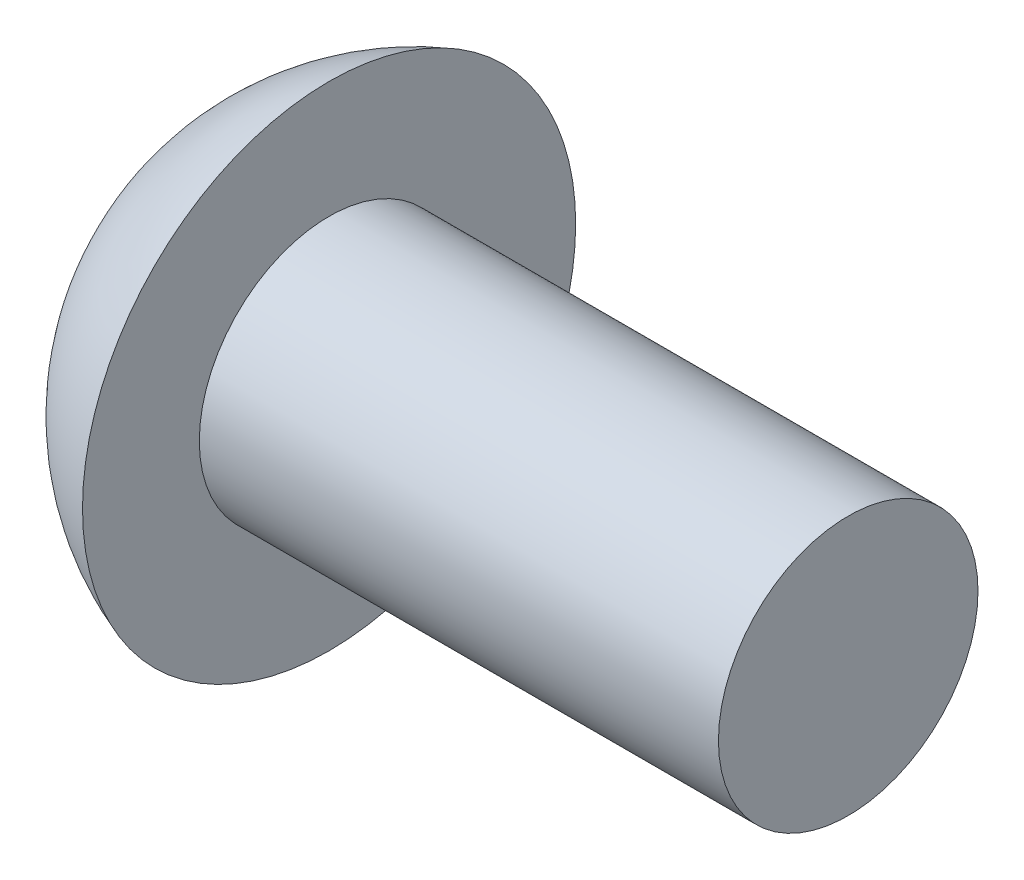
SolidWorks part; units mm, degrees
ref_plane "Front" through (0, 0, 0) normal (0, 0, 1) x (1, 0, 0)
ref_plane "Top" through (0, 0, 0) normal (0, 1, 0) x (1, 0, 0)
ref_plane "Right" through (0, 0, 0) normal (1, 0, 0) x (0, 0, -1)
sketch "Sketch1" plane through (0, 0, 0) normal (1, 0, 0) x (0, 0, -1)
  line L0 (0, 0) -> (1.4, 0) construction
  circle A0 centre (0, 0) radius 3.8
extrude "BaseHead" add sketch "Sketch1" along normal blind 2.2
sketch "Sketch2" plane through (2.2, 0, 0) normal (1, 0, 0) x (0, 0, -1)
  circle A0 centre (0, 0) radius 2
extrude "BaseBody" add sketch "Sketch2" along normal blind 8
cosmetic thread "ThreadCosmetic1" parameters "D1"=6.6, "THD_MINOR"=3.242
fillet "HeadFillet" [suppressed] radius 0.2
sketch "Sketch3" plane through (-13.4796, 2.4796, 0) normal (0, 0, 1) x (0, -1, 0)
  line L0 (2.4796, 13.4796) -> (2.4796, 41.0387) construction
  line L3 (-1.3204, 13.4796) -> (2.4796, 13.4796) construction
  line L5 (-6.3204, 15.6796) -> (-6.3204, 8.4796)
  line L6 (0.5446, 13.4796) -> (0.5446, 8.4796)
  line L7 (0.5446, 8.4796) -> (-6.3204, 8.4796)
  line L8 (-6.3204, 15.6796) -> (-1.3204, 15.6796)
  line L9 (-1.3204, 13.4796) -> (6.2796, 13.4796) construction
  arc A0 (-1.3204, 15.6796) -> (0.5446, 13.4796) centre (2.4796, 17.0104) ccw
  dimension "D2" = 5
  dimension "e" = 3.87
  dimension "D3" = 5
revolve "Cut-Revolve1" cut sketch "Sketch3" angle 360 about L0
sketch "Sketch4" plane through (0, 0, 0) normal (1, 0, 0) x (0, 0, -1)
  line L1 (1.4434, 0) -> (0.7217, 1.25)
  line L2 (0.7217, 1.25) -> (-0.7217, 1.25)
  line L3 (-0.7217, 1.25) -> (-1.4434, 0)
  line L4 (-1.4434, 0) -> (-0.7217, -1.25)
  line L5 (-0.7217, -1.25) -> (0.7217, -1.25)
  line L6 (0.7217, -1.25) -> (1.4434, 0)
  circle A0 centre (0, 0) radius 1.25 construction
  dimension "s" = 2.5
extrude "HexagonSocket" cut sketch "Sketch4" along normal blind 1.3
sketch "Sketch5" plane through (1.3, 0, 0) normal (-1, 0, 0) x (0, 0, 1)
  line L0 (0.7217, -1.25) -> (-0.7217, -1.25) construction
  line L1 (-0.7217, -1.25) -> (-1.4434, 0) construction
  line L2 (1.4434, 0) -> (0.7217, -1.25) construction
  line L3 (0.7217, 1.25) -> (1.4434, 0) construction
  line L4 (-1.4434, 0) -> (-0.7217, 1.25) construction
  line L5 (-0.7217, 1.25) -> (0.7217, 1.25) construction
  line L6 (0.7217, -1.25) -> (-0.7217, -1.25)
  line L7 (-0.7217, -1.25) -> (-1.4434, 0)
  line L8 (1.4434, 0) -> (0.7217, -1.25)
  line L9 (0.7217, 1.25) -> (1.4434, 0)
  line L10 (-1.4434, 0) -> (-0.7217, 1.25)
  line L11 (-0.7217, 1.25) -> (0.7217, 1.25)
extrude "Cut-Extrude2" cut sketch "Sketch5" against normal blind 5 draft 60
sketch "Sketch6" plane through (0, 0, 0) normal (0, 0, 1) x (1, 0, 0)
  line L0 (10.2, 1.6718) -> (10.3895, 2)
  line L1 (10.3895, 2) -> (10.3895, 2.379)
  line L2 (10.3895, 2.379) -> (10.0105, 2.379)
  line L3 (10.0105, 2.379) -> (10.0105, 2)
  line L4 (10.0105, 2) -> (10.2, 1.6718)
  line L5 (0, 0) -> (24.7294, 0) construction
  line L6 (10.2, -2) -> (10.2, 2) construction
  dimension "D1" = 0.379
  dimension "D2" = 4
revolve "Cut-Revolve10" [suppressed] cut sketch "Sketch6" angle 360 about L5
pattern_linear "LPattern10" [suppressed] count 16 spacing 0.4548 along (-1, 0, 0) of bodies 106
equation "\"D1@ThreadCosmetic1\" = \"l@BaseBody\" - \"a@Sketch1\""
equation "\"D2@Sketch6\" = \"d@Sketch2\""
equation "\"D1@Sketch6\" =  (\"d@Sketch2\" - \"THD_MINOR@ThreadCosmetic1\" )  / 2"
equation "\"D3@LPattern10\" = \"D1@Sketch6\" * 1.2"
equation "\"D1@LPattern10\" = \"D1@ThreadCosmetic1\" / \"D3@LPattern10\" + 1"
